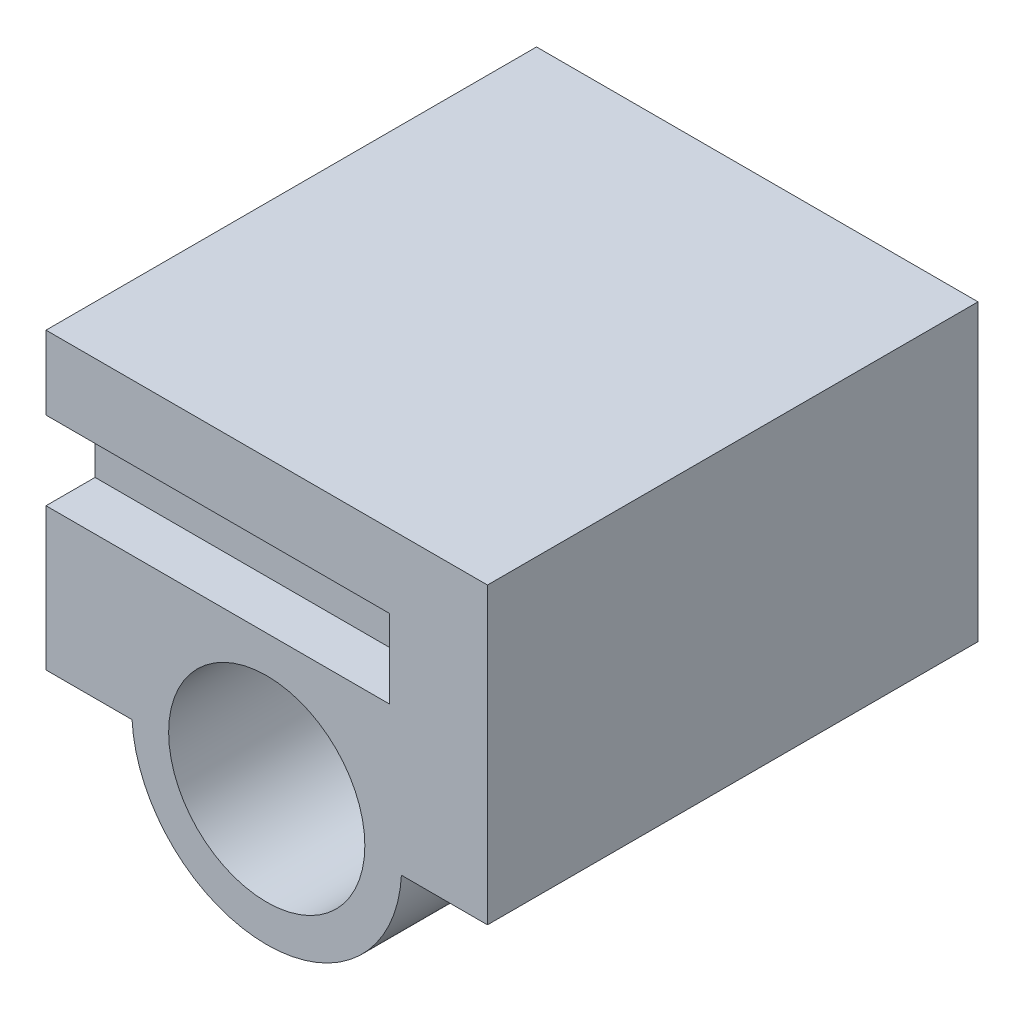
SolidWorks part; units mm, degrees
ref_plane "Front Plane" through (0, 0, 0) normal (0, 0, 1) x (1, 0, 0)
ref_plane "Top Plane" through (0, 0, 0) normal (0, 1, 0) x (1, 0, 0)
ref_plane "Right Plane" through (0, 0, 0) normal (1, 0, 0) x (0, 0, -1)
sketch "Sketch1" plane through (0, 0, 0) normal (0, 0, 1) x (1, 0, 0)
  line L1 (-4.5, 3) -> (4.5, 3)
  line L2 (-4.5, 3) -> (-4.5, -3)
  line L3 (-4.5, -3) -> (4.5, -3)
  line L4 (4.5, 3) -> (4.5, -3)
  line L5 (-4.5, 3) -> (4.5, -3) construction
  line L6 (-4.5, -3) -> (4.5, 3) construction
  point P0 (0, 0)
  dimension "D1" = 9
  dimension "D2" = 6
extrude "Boss-Extrude1" add sketch "Sketch1" along normal blind 10
sketch "Sketch2" plane through (4.5, 0, 0) normal (1, 0, 0) x (0, 0, -1)
  line L0 (-10, -3) -> (-10, 3) construction
  line L1 (-10, 1.5) -> (0, 1.5)
  line L2 (-10, 1.5) -> (-10, -0.1)
  line L3 (-10, -0.1) -> (0, -0.1)
  line L4 (0, 1.5) -> (0, -0.1)
  line L5 (0, -3) -> (0, 3) construction
  line L6 (-10, 3) -> (0, 3) construction
  dimension "D1" = 1.6
  dimension "D2" = 1.5
extrude "Cut-Extrude1" cut sketch "Sketch2" against normal blind 7 from offset 2 offset against normal yes
sketch "Sketch3" plane through (0, 0, 10) normal (0, 0, 1) x (1, 0, 0)
  line L0 (0, 0) -> (0, -3) construction
  line L1 (-4.5, -3) -> (4.5, -3) construction
  line L3 (-4.5, -0.1) -> (2.5, -0.1) construction
  circle A0 centre (0, -2.85) radius 2.75
  dimension "D1" = 5.5
  dimension "D2" = 2.75
extrude "Boss-Extrude2" add sketch "Sketch3" against normal through all
sketch "Sketch4" plane through (0, 0, 10) normal (0, 0, 1) x (1, 0, 0)
  circle A0 centre (0, -2.85) radius 2
  arc A1 (-2.7459, -3) -> (2.7459, -3) centre (0, -2.85) ccw construction
  dimension "D1" = 4
extrude "Cut-Extrude2" cut sketch "Sketch4" against normal blind 7
sketch "Sketch5" plane through (-4.5, 0, 0) normal (-1, 0, 0) x (0, 0, 1)
  line L0 (10, -0.1) -> (0, -0.1) construction
  line L2 (0, -0.1) -> (1, -0.1)
  line L3 (0, -0.1) -> (0, 0.65)
  line L4 (0.15, 0.8) -> (0.85, 0.8)
  line L5 (1, -0.1) -> (1, 0.65)
  line L6 (0, -0.1) -> (0, 1.5) construction
  line L7 (2, -0.1) -> (2, 0.65)
  line L8 (2.15, 0.8) -> (2.85, 0.8)
  line L9 (3, -0.1) -> (3, 0.65)
  line L10 (2, -0.1) -> (3, -0.1)
  line L11 (4, -0.1) -> (4, 0.65)
  line L12 (4.15, 0.8) -> (4.85, 0.8)
  line L13 (5, -0.1) -> (5, 0.65)
  line L14 (4, -0.1) -> (5, -0.1)
  line L15 (6, -0.1) -> (6, 0.65)
  line L16 (6.15, 0.8) -> (6.85, 0.8)
  line L17 (7, -0.1) -> (7, 0.65)
  line L18 (6, -0.1) -> (7, -0.1)
  line L19 (8, -0.1) -> (8, 0.65)
  line L20 (8.15, 0.8) -> (8.85, 0.8)
  line L21 (9, -0.1) -> (9, 0.65)
  line L22 (8, -0.1) -> (9, -0.1)
  arc A0 (0, 0.65) -> (0.15, 0.8) centre (0.15, 0.65) cw
  arc A1 (0.85, 0.8) -> (1, 0.65) centre (0.85, 0.65) cw
  arc A2 (2, 0.65) -> (2.15, 0.8) centre (2.15, 0.65) cw
  arc A3 (2.85, 0.8) -> (3, 0.65) centre (2.85, 0.65) cw
  arc A4 (4, 0.65) -> (4.15, 0.8) centre (4.15, 0.65) cw
  arc A5 (4.85, 0.8) -> (5, 0.65) centre (4.85, 0.65) cw
  arc A6 (6, 0.65) -> (6.15, 0.8) centre (6.15, 0.65) cw
  arc A7 (6.85, 0.8) -> (7, 0.65) centre (6.85, 0.65) cw
  arc A8 (8, 0.65) -> (8.15, 0.8) centre (8.15, 0.65) cw
  arc A9 (8.85, 0.8) -> (9, 0.65) centre (8.85, 0.65) cw
  point P8 (0, 0.8)
  point P11 (1, 0.8)
  dimension "D2" = 0.15
  dimension "D1" = 1
  dimension "D3" = 0.75
  dimension "D4" = 0
  dimension "D6" = 2
  dimension "D5" = 5
extrude "Boss-Extrude3" add sketch "Sketch5" against normal up to next
